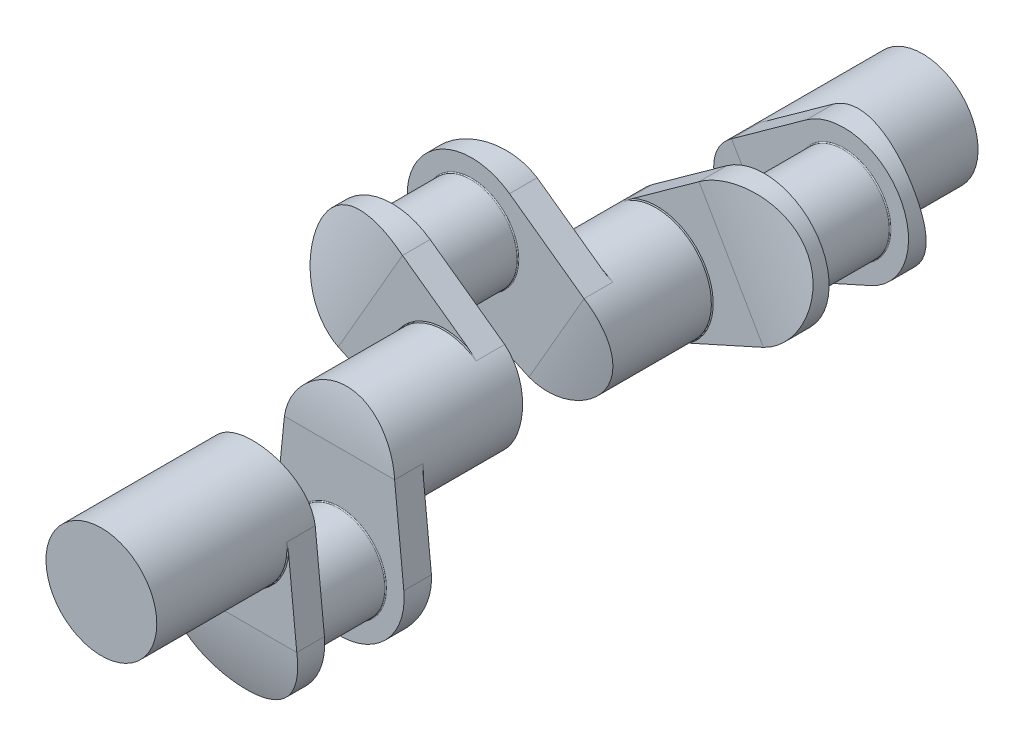
SolidWorks part; units mm, degrees
ref_plane "Front Plane" through (0, 0, 0) normal (0, 0, 1) x (1, 0, 0)
ref_plane "Top Plane" through (0, 0, 0) normal (0, 1, 0) x (1, 0, 0)
ref_plane "Right Plane" through (0, 0, 0) normal (1, 0, 0) x (0, 0, -1)
sketch "Sketch2" plane through (0, 0, 0) normal (0, 0, 1) x (1, 0, 0)
  circle A0 centre (0, 0) radius 31.75
  dimension "D1" = 63.5
extrude "Boss-Extrude1" add sketch "Sketch2" along normal blind 27.31
sketch "Sketch3" plane through (0, 0, 27.31) normal (0, 0, 1) x (1, 0, 0)
  line L0 (-37.909, 67.31) -> (-44.2272, 4.445)
  line L1 (37.909, 67.31) -> (44.2272, 4.445)
  arc A0 (-44.2272, 4.445) -> (44.2272, 4.445) centre (0, 0) ccw
  circle A2 centre (0, 0) radius 31.75 construction
  arc A3 (37.909, 67.31) -> (-37.909, 67.31) centre (0, 63.5) ccw
  dimension "D1" = 12.7
  dimension "D3" = 63.5
extrude "Boss-Extrude2" add sketch "Sketch3" along normal blind 19
sketch "Sketch4" plane through (0, 0, 46.31) normal (0, 0, 1) x (1, 0, 0)
  circle A0 centre (0, 63.5) radius 38.1
  dimension "D1" = 76.2
extrude "Boss-Extrude3" add sketch "Sketch4" along normal blind 26.67
sketch "Sketch5" plane through (0, 0, 0) normal (1, 0, 0) x (0, 0, -1)
  line L0 (-46.31, -44.45) -> (-27.31, -44.45) construction
  line L1 (-36.81, -44.45) -> (-59.0738, -44.45)
  line L2 (-59.0738, -44.45) -> (-59.0738, 4.445)
  line L3 (-59.0738, 4.445) -> (-46.31, 4.445)
  line L4 (-27.31, 101.6) -> (-72.98, 101.6) construction
  line L5 (-32.31, 101.6) -> (-8.0236, 101.6)
  line L6 (-8.0236, 101.6) -> (-8.0236, 67.31)
  line L7 (-8.0236, 67.31) -> (-27.31, 67.31)
  arc A0 (-46.31, 4.445) -> (-36.81, -44.45) centre (122.5264, 11.8785) ccw
  arc A1 (-27.31, 67.31) -> (-32.31, 101.6) centre (-196.1603, 60.1986) ccw
  dimension "D1" = 169
  dimension "D3" = 169
  dimension "D2" = 5
extrude "Cut-Extrude1" cut sketch "Sketch5" against normal through all both and the other way through all contours L7 A1 L5 L6 | L3 A0 L1 L2
fillet "Fillet1" radius 0.64 2 edges at (0, 25.4, 46.31) (31.75, 0, 27.31)
mirror "Mirror1" about plane through (0, 0, 0) normal (0, 0, 1) of bodies 104
pattern_linear "LPattern1" count 3 spacing 145.96 along (0, 0, 1) of bodies 105
ref_axis "Axis1" through (0, 63.5, 422.775) along (0, 0, -1)
move or copy body "Body-Move/Copy1" bodies to move or copy 106 copy no rotation origin (0, 63.5, 0) rotation axis (0, 0, -1) rotation angle 120
move or copy body "Body-Move/Copy2" bodies to move or copy 105 copy no rotation origin (0, 63.5, 0) rotation axis (0, 0, 1) rotation angle 120
combine bodies "Combine1" operation type add bodies to combine 107 108 109
sketch "Sketch6" plane through (0, 0, 364.9) normal (0, 0, 1) x (1, 0, 0)
  circle A1 centre (0, 63.5) radius 38.1
  circle A2 centre (0, 63.5) radius 38.1
  dimension "D1" = 0
extrude "Boss-Extrude4" add sketch "Sketch6" along normal blind 63.5 contours A2
sketch "Sketch8" plane through (0, 0, -72.98) normal (0, 0, -1) x (-1, 0, 0)
  circle A1 centre (0, 63.5) radius 38.1
  circle A2 centre (0, 63.5) radius 38.1
  dimension "D1" = 0
extrude "Boss-Extrude5" add sketch "Sketch8" along normal blind 63.5
